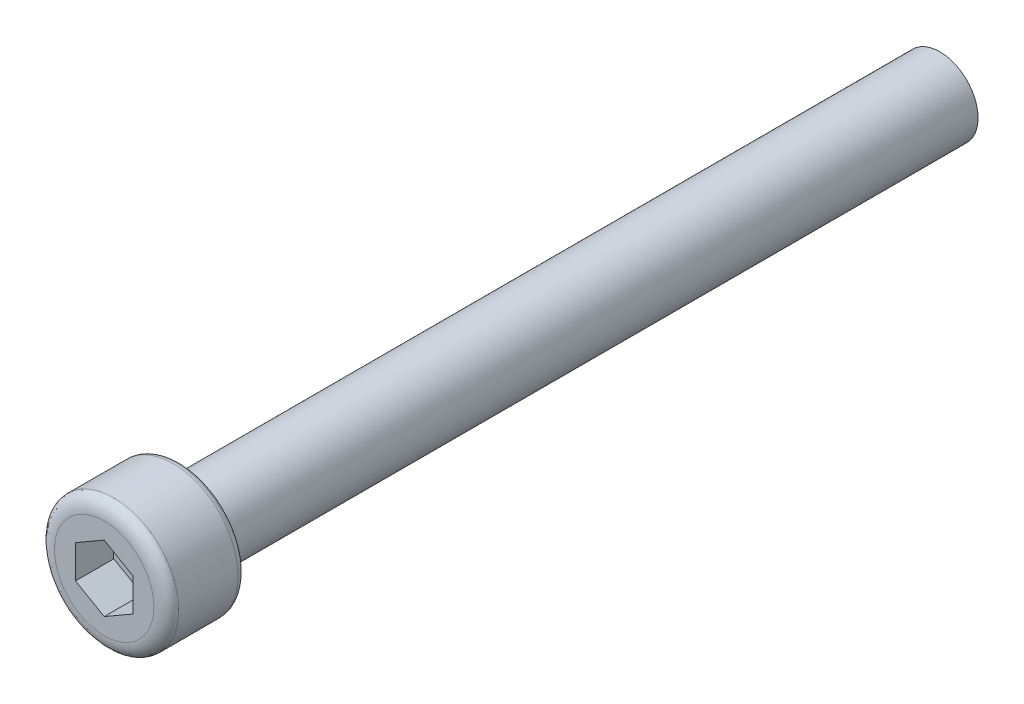
SolidWorks part; units mm, degrees
ref_plane "前视基准面" through (0, 0, 0) normal (0, 0, 1) x (1, 0, 0)
ref_plane "上视基准面" through (0, 0, 0) normal (0, 1, 0) x (1, 0, 0)
ref_plane "右视基准面" through (0, 0, 0) normal (1, 0, 0) x (0, 0, -1)
sketch "草图2" plane through (0, 0, 0) normal (1, 0, 0) x (0, 0, -1)
  line L0 (-22, 0) -> (-22, 3.4)
  line L1 (-22, 3.4) -> (-18, 3.4)
  line L2 (-18, 3.4) -> (-18, 2)
  line L3 (-18, 2) -> (22, 2)
  line L4 (22, 2) -> (22, 0)
  line L5 (22, 0) -> (-22, 0)
  dimension "D1" = 40
  dimension "D2" = 3.4
  dimension "D3" = 2
  dimension "D4" = 4
revolve "旋转1" add sketch "草图2" angle 360 about L5
chamfer "倒角1" distance 0.3 angle 60 1 edges at (-2, 0, -22) first distance on face at (-2, 0, 18)
fillet "圆角1" radius 0.4 1 edges at (-3.4, 0, 18)
fillet "圆角2" radius 0.8 1 edges at (-3.4, 0, 22) second distance 0.5 first distance on face at (-3.4, 0, 22)
sketch "草图3" plane through (0, 0, 22) normal (0, 0, 1) x (1, 0, 0)
  line L1 (0, 1.7321) -> (-1.5, 0.866)
  line L2 (-1.5, 0.866) -> (-1.5, -0.866)
  line L3 (-1.5, -0.866) -> (0, -1.7321)
  line L4 (0, -1.7321) -> (1.5, -0.866)
  line L5 (1.5, -0.866) -> (1.5, 0.866)
  line L6 (1.5, 0.866) -> (0, 1.7321)
  circle A0 centre (0, 0) radius 1.5 construction
  dimension "D1" = 3
extrude "切除-拉伸1" cut sketch "草图3" against normal blind 2
